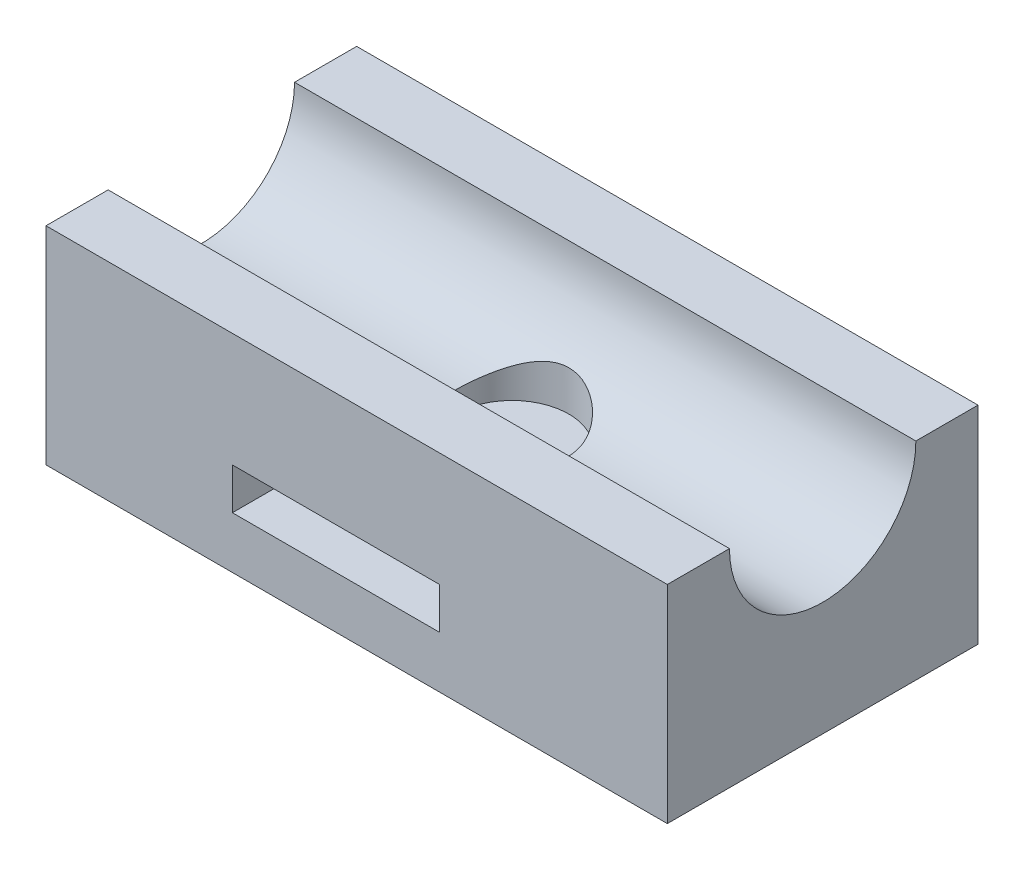
SolidWorks part; units mm, degrees
ref_plane "Front Plane" through (0, 0, 0) normal (0, 0, 1) x (1, 0, 0)
ref_plane "Top Plane" through (0, 0, 0) normal (0, 1, 0) x (1, 0, 0)
ref_plane "Right Plane" through (0, 0, 0) normal (1, 0, 0) x (0, 0, -1)
sketch "Sketch1" plane through (0, 0, 0) normal (0, 1, 0) x (1, 0, 0)
  line L1 (-0.0107, 38.1) -> (76.1893, 38.1)
  line L2 (-0.0107, 38.1) -> (-0.0107, 0)
  line L3 (-0.0107, 0) -> (76.1893, 0)
  line L4 (76.1893, 38.1) -> (76.1893, 0)
  dimension "D1" = 76.2
  dimension "D2" = 38.1
  dimension "D3" = 0.0107
extrude "Boss-Extrude1" add sketch "Sketch1" along normal blind 25.4
sketch "Sketch2" plane through (-0.0107, 0, 0) normal (-1, 0, 0) x (0, 0, 1)
  line L0 (-38.1, 25.4) -> (0, 25.4) construction
  circle A0 centre (-19.05, 25.4) radius 11.43
  dimension "D1" = 22.86
extrude "Cut-Extrude1" cut sketch "Sketch2" against normal through all
sketch "Sketch3" plane through (0, 0, 0) normal (0, -1, 0) x (1, 0, 0)
  line L0 (-0.0107, -38.1) -> (-0.0107, 0) construction
  line L2 (-0.0107, 0) -> (76.1893, 0) construction
  circle A2 centre (38.0893, -19.05) radius 3.302
  circle A3 centre (38.0893, -19.05) radius 6.985
  point P0 (0, 0)
  dimension "D1" = 19.05
  dimension "D2" = 38.1
sketch "Sketch5" plane through (0, 0, -38.1) normal (0, 0, -1) x (-1, 0, 0)
  line L1 (-48.2493, 11.43) -> (-22.8493, 11.43)
  line L2 (-48.2493, 11.43) -> (-48.2493, 6.35)
  line L3 (-48.2493, 6.35) -> (-22.8493, 6.35)
  line L4 (-22.8493, 11.43) -> (-22.8493, 6.35)
  dimension "D1" = 25.4
  dimension "D2" = 5.08
  dimension "D3" = 22.86
  dimension "D4" = 6.35
extrude "Cut-Extrude3" cut sketch "Sketch5" against normal through all
extrude "Cut-Extrude6" cut sketch "Sketch3" against normal through all contours A2 region at (38.0893, 0, -19.05)
extrude "Cut-Extrude7" cut sketch "Sketch3<3>" along normal blind 10.16 from offset 17.78 offset against normal yes
sketch "Sketch3<3>" plane through (0, 0, 0) normal (0, -1, 0) x (1, 0, 0) same geometry as "Sketch3"
